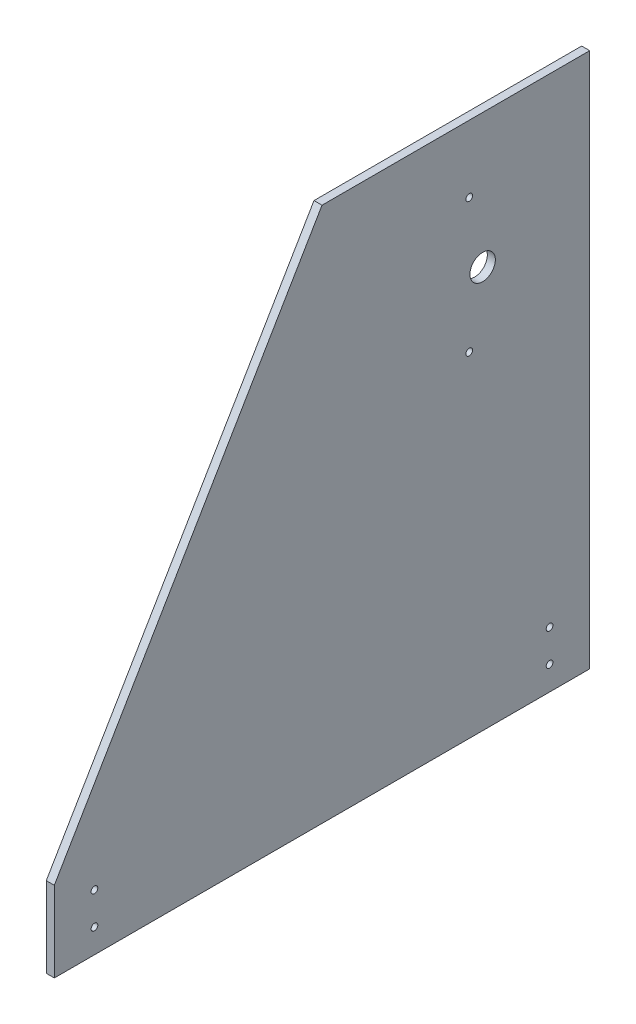
SolidWorks part; units mm, degrees
ref_plane "Front Plane" through (0, 0, 0) normal (0, 0, 1) x (1, 0, 0)
ref_plane "Top Plane" through (0, 0, 0) normal (0, 1, 0) x (1, 0, 0)
ref_plane "Right Plane" through (0, 0, 0) normal (1, 0, 0) x (0, 0, -1)
sketch "Sketch1" plane through (0, 0, 0) normal (1, 0, 0) x (0, 0, -1)
  line L0 (0, -2343.7616) -> (0, 114844.3172) construction
  line L1 (-2343.7616, 0) -> (114844.3172, 0) construction
  line L2 (0, 60) -> (400, 60) construction
  line L3 (0, 0) -> (400, 0)
  line L5 (200, 400) -> (400, 400)
  line L6 (400, 0) -> (400, 400)
  line L7 (0, 60) -> (200, 400)
  line L8 (0, 60) -> (0, 0)
  line L9 (-1000, 30) -> (49000, 30) construction
  line L10 (200, -1000) -> (200, 49000) construction
  line L11 (310, -1000) -> (310, 49000) construction
  line L12 (320, -1008.4066) -> (320, 48991.5934) construction
  line L13 (298.2689, 300) -> (341.7311, 300) construction
  circle A0 centre (30, 42) radius 2.5
  circle A2 centre (30, 18) radius 2.5
  circle A3 centre (370, 18) radius 2.5
  circle A4 centre (370, 42) radius 2.5
  circle A5 centre (310, 350) radius 2.5
  circle A6 centre (310, 250) radius 2.5
  circle A7 centre (320, 300) radius 9.5
  point P14 (0, 30)
  point P21 (200, 0)
  point P38 (320, 300)
  dimension "D7" = 5
  dimension "D9" = 5
  dimension "D14" = 19
  dimension "D1" = 400
  dimension "D2" = 400
  dimension "D3" = 60
  dimension "D4" = 200
  dimension "D5" = 30
  dimension "D6" = 90
  dimension "D8" = 12
  dimension "D10" = 50
  dimension "D11" = 100
  dimension "D12" = 80
  dimension "D13" = 50
extrude "Boss-Extrude1" add sketch "Sketch1" along normal blind 6
